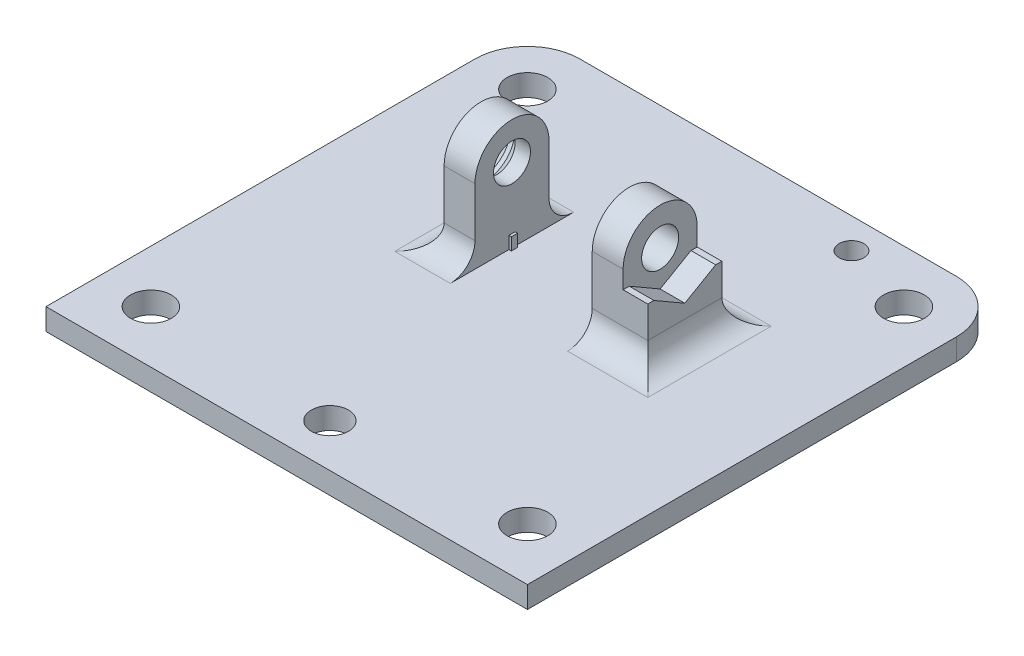
SolidWorks part; units mm, degrees
ref_plane "Front Plane" through (0, 0, 0) normal (0, 0, 1) x (1, 0, 0)
ref_plane "Top Plane" through (0, 0, 0) normal (0, 1, 0) x (1, 0, 0)
ref_plane "Right Plane" through (0, 0, 0) normal (1, 0, 0) x (0, 0, -1)
sketch "Sketch1" plane through (0, 0, 0) normal (0, 1, 0) x (1, 0, 0)
  line L0 (-19.5, 35.2) -> (-19.5, -19.5) construction
  line L1 (-19.5, 19.5) -> (19.5, 19.5)
  line L2 (-19.5, 19.5) -> (-19.5, -19.5)
  line L3 (-19.5, -19.5) -> (19.5, -19.5)
  line L4 (19.5, 19.5) -> (19.5, -19.5)
  line L5 (-19.5, 19.5) -> (19.5, -19.5) construction
  line L6 (-19.5, -19.5) -> (19.5, 19.5) construction
  line L7 (-19.5, -19.5) -> (19.5, -19.5) construction
  line L8 (0, -19.5) -> (0, 19.5) construction
  circle A0 centre (-15.25, -15.25) radius 1.65 construction
  circle A1 centre (15.25, -15.25) radius 1.65 construction
  circle A2 centre (9.2, 17.05) radius 1 construction
  circle A3 centre (15.25, 15.25) radius 1.65 construction
  circle A4 centre (-15.25, 15.25) radius 1.65 construction
  circle A5 centre (-15.25, -15.25) radius 1.65
  circle A6 centre (15.25, -15.25) radius 1.65
  circle A7 centre (9.2, 17.05) radius 1
  circle A8 centre (15.25, 15.25) radius 1.65
  circle A9 centre (-15.25, 15.25) radius 1.65
  circle A10 centre (-15.25, 15.25) radius 4.25
  circle A11 centre (15.25, 15.25) radius 4.25
  circle A12 centre (-15.25, -15.25) radius 4.25
  circle A13 centre (15.25, -15.25) radius 4.25
  circle A14 centre (0, -16) radius 1.5
  point P0 (0, 0)
  dimension "D1" = 3
  dimension "D2" = 3.5
extrude "Shape" add sketch "Sketch1" along normal blind 1.75 contours A13 L4 A11 L1 A10 L2 A12 L3 A7 | A10 A9 | A11 A8 | A13 A6 | A12 A5 | A12 L2 L3 | A13 L3 L4 region at (-0.0228, 0, -0.0469) region at (-12.3298, 0, -18.1702) region at (18.1702, 0, -18.1702) region at (-18.5507, 0, 18.5507) region at (-15.25, 0, 11.1202) region at (18.1702, 0, 18.1702) region at (18.5507, 0, 18.5507)
sketch "Sketch3" plane through (0, 1.75, 0) normal (0, 1, 0) x (1, 0, 0)
  line L0 (0, 19.5) -> (0, -19.5) construction
  line L1 (-15.25, 19.5) -> (15.25, 19.5) construction
  line L2 (-19.5, -19.5) -> (19.5, -19.5) construction
  line L3 (-19.5, 3.5) -> (19.5, 3.5) construction
  line L4 (-19.5, 15.25) -> (-19.5, -19.5) construction
  line L5 (19.5, 15.25) -> (19.5, -19.5) construction
  line L6 (4.75, 6.5) -> (7.25, 6.5)
  line L7 (-4.75, 6.5) -> (-7.25, 6.5)
  line L8 (-4.75, 6.5) -> (-4.75, 0.5)
  line L9 (-4.75, 0.5) -> (-7.25, 0.5)
  line L10 (-7.25, 6.5) -> (-7.25, 0.5)
  line L11 (-4.75, 6.5) -> (-7.25, 0.5) construction
  line L12 (-4.75, 0.5) -> (-7.25, 6.5) construction
  line L13 (4.75, 6.5) -> (4.75, 0.5)
  line L14 (4.75, 0.5) -> (7.25, 0.5)
  line L15 (7.25, 6.5) -> (7.25, 0.5)
  line L17 (7.25, 6.5) -> (9.25, 6.5)
  line L18 (7.25, 6.5) -> (7.25, 0.5)
  line L19 (7.25, 0.5) -> (9.25, 0.5)
  line L20 (9.25, 6.5) -> (9.25, 0.5)
  point P12 (-6, 3.5)
  dimension "D1" = 16
  dimension "D2" = 9.5
  dimension "D3" = 2.5
  dimension "D4" = 6
  dimension "D5" = 4.5
extrude "Supports" add sketch "Sketch3" along normal blind 9 contours L7 L10 L9 L8 | L15 L6 L13 L14 | L20 L17 L15 L19 region at (6, 1.75, -3.5) region at (8.25, 1.75, -3.5) region at (-6, 1.75, -3.5)
sketch "Sketch4" plane through (-7.25, 0, 0) normal (-1, 0, 0) x (0, 0, 1)
  line L0 (-3.5, 10.75) -> (-3.5, 1.75) construction
  line L2 (-6.5, 1.75) -> (-0.5, 1.75) construction
  line L3 (-0.5, 10.75) -> (-0.5, 1.75) construction
  line L4 (-6.5, 10.75) -> (-0.5, 10.75) construction
  circle A0 centre (-3.5, 7.75) radius 3
  circle A1 centre (-3.5, 7.75) radius 1.5
  line M2 (-0.5, 1.75) -> (-0.5, 10.75)
  line M4 (-6.5, 10.75) -> (-6.5, 1.75)
  line M11 (-0.5, 10.75) -> (-6.5, 10.75)
  dimension "D1" = 3
extrude "Support cuts" cut sketch "Sketch4" against normal up to surface (16.5 mm away) contours A1 L0 | L0 A1 | A0 M11 M4 | A0 M2 M11 region at (-7.25, 10.0799, -1.1701) region at (-7.25, 10.0799, -5.8299) region at (-7.25, 7.75, -2.8634) region at (-7.25, 7.75, -4.1366) up to face at (9.25, 6.25, -3.5)
fillet "Fillet1" radius 2 6 edges at (-6, 1.75, -6.5) (7, 1.75, -6.5) (7, 1.75, -0.5) (-6, 1.75, -0.5) (-7.25, 1.75, -3.5) (9.25, 1.75, -3.5)
sketch "Sketch5" plane through (9.25, 0, 0) normal (1, 0, 0) x (0, 0, -1)
  line L0 (1, 6.3066) -> (0.5, 6.3066)
  line L1 (3.5, 4.8632) -> (6, 6.3066)
  line L2 (6, 6.3066) -> (6, 9.1934)
  line L3 (6, 9.1934) -> (3.5, 10.6368)
  line L4 (3.5, 10.6368) -> (1, 9.1934)
  line L5 (1, 9.1934) -> (1, 6.3066)
  line L6 (1, 6.3066) -> (3.5, 4.8632)
  line L7 (6, 6.3066) -> (6.5, 6.3066)
  line L9 (0.5, 7.75) -> (0.5, 3.75)
  line L10 (0.5, 3.75) -> (6.5, 3.75)
  line L11 (6.5, 3.75) -> (6.5, 7.75)
  line L12 (0.5, 7.75) -> (0.5, 3.75)
  line L13 (0.5, 3.75) -> (6.5, 3.75)
  line L14 (6.5, 3.75) -> (6.5, 7.75)
  circle A0 centre (3.5, 7.75) radius 2.5 construction
  circle A1 centre (3.5, 7.75) radius 1.5 construction
  arc A2 (6.5, 7.75) -> (0.5, 7.75) centre (3.5, 7.75) ccw
  arc A3 (6.5, 7.75) -> (0.5, 7.75) centre (3.5, 7.75) ccw
  circle M3 centre (3.5, 7.75) radius 1.5
  line M4 (0.5, 7.75) -> (0.5, 3.75)
  line M6 (6.5, 3.75) -> (6.5, 7.75)
  arc M7 (6.5, 7.75) -> (0.5, 7.75) centre (3.5, 7.75) ccw
  dimension "D1" = 5
  dimension "D2" = 0
extrude "Nut holder" cut sketch "Sketch5" against normal blind 2 contours L5 L6 L1 L2 L3 L4 M3 | L2 L7 L0 L5 L4 L3 M6 M7 M4 region at (9.25, 6.3813, -0.75) region at (9.25, 7.75, -1.0764)
sketch "Sketch6" plane through (-7.25, 0, 0) normal (-1, 0, 0) x (0, 0, 1)
  circle A0 centre (-3.5, 7.75) radius 2.4
  dimension "D1" = 4.8
extrude "Screw cut" cut sketch "Sketch6" against normal blind 0.35
chamfer "Scew chamfer" distance 0.9 angle 45 1 edges at (-6.9, 7.75, -2)
sketch "Sketch7" plane through (4.75, 0, 0) normal (-1, 0, 0) x (0, 0, 1)
  line L0 (-3.5, 1.75) -> (-3.5, 10.75) construction
  line L1 (-8.5, 1.75) -> (1.5, 1.75) construction
  line L3 (-3.25, 2.75) -> (-3.75, 2.75)
  line L4 (-3.25, 2.75) -> (-3.25, 1.75)
  line L5 (-3.25, 1.75) -> (-3.75, 1.75)
  line L6 (-3.75, 2.75) -> (-3.75, 1.75)
  line L7 (-3.25, 2.75) -> (-3.75, 1.75) construction
  line L8 (-3.25, 1.75) -> (-3.75, 2.75) construction
  arc A0 (-0.5, 7.75) -> (-6.5, 7.75) centre (-3.5, 7.75) ccw construction
  point P7 (-3.5, 2.25)
  dimension "D1" = 0.5
  dimension "D2" = 1
extrude "Angle fix 1" add sketch "Sketch7" along normal blind 0.2
sketch "Sketch8" plane through (-4.75, 0, 0) normal (1, 0, 0) x (0, 0, -1)
  line L4 (3.75, 1.75) -> (3.75, 2.75)
  line L5 (3.25, 1.75) -> (3.75, 1.75)
  line L6 (3.25, 2.75) -> (3.25, 1.75)
  line L7 (3.75, 2.75) -> (3.25, 2.75)
  line L8 (3.75, 1.75) -> (3.75, 2.75)
  line L9 (3.25, 1.75) -> (3.75, 1.75)
  line L10 (3.25, 2.75) -> (3.25, 1.75)
  line L11 (3.75, 2.75) -> (3.25, 2.75)
  dimension "D1" = 0
extrude "Angle fix 2" add sketch "Sketch8" along normal blind 0.2
